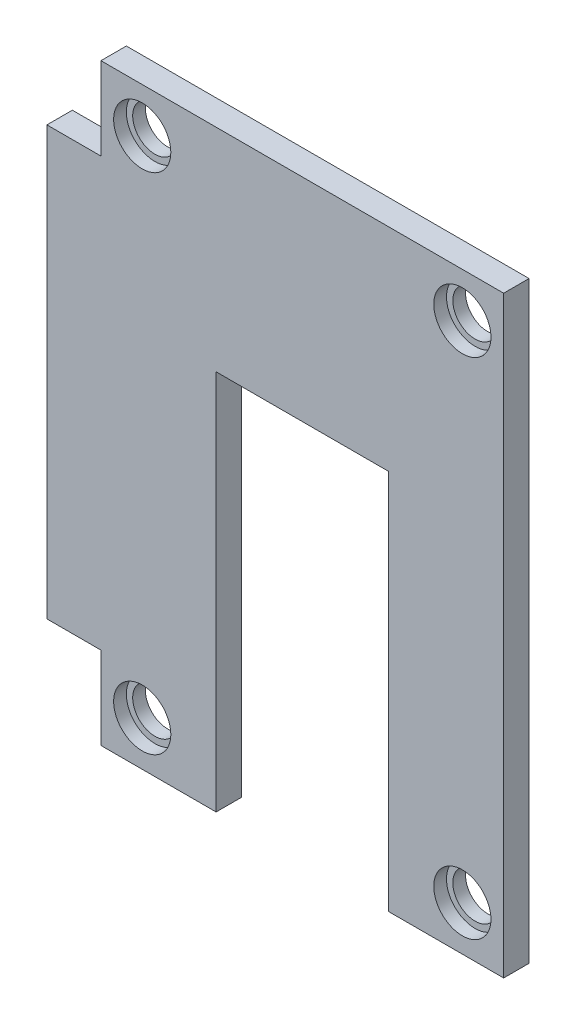
SolidWorks part; units mm, degrees
ref_plane "Alzado" through (0, 0, 0) normal (0, 0, 1) x (1, 0, 0)
ref_plane "Planta" through (0, 0, 0) normal (0, 1, 0) x (1, 0, 0)
ref_plane "Vista lateral" through (0, 0, 0) normal (1, 0, 0) x (0, 0, -1)
sketch "Croquis1" plane through (0, 0, 0) normal (0, 0, 1) x (1, 0, 0)
  line L0 (0, 93.345) -> (64.3868, 93.345)
  line L1 (0, 93.345) -> (0, 0)
  line L2 (0, 0) -> (64.3868, 0)
  line L3 (64.3868, 93.345) -> (64.3868, 0)
  dimension "D1" = 64.3868
  dimension "D2" = 93.345
extrude "Saliente-Extruir1" add sketch "Croquis1" along normal blind 4
sketch "Croquis2" plane through (0, 0, 4) normal (0, 0, 1) x (1, 0, 0)
  line L5 (0, 0) -> (64.3868, 0) construction
  line L6 (18.63, 0) -> (45.7568, 0)
  line L7 (18.63, 0) -> (18.63, 60)
  line L8 (18.63, 60) -> (45.7568, 60)
  line L9 (45.7568, 0) -> (45.7568, 60)
  line L10 (64.3868, 0) -> (64.3868, 93.345) construction
  line L11 (0, 93.345) -> (0, 0) construction
  dimension "D1" = 18.63
  dimension "D2" = 18.63
  dimension "D3" = 60
extrude "Cortar-Extruir1" cut sketch "Croquis2" against normal through all
sketch "Croquis5" plane through (0, 0, 4) normal (0, 0, 1) x (1, 0, 0)
  line L0 (64.3868, 0) -> (64.3868, 93.345) construction
  line L1 (64.3868, 93.345) -> (0, 93.345) construction
  line L2 (0, 93.345) -> (0, 0) construction
  line L3 (45.7568, 0) -> (64.3868, 0) construction
  circle A0 centre (57.3868, 86.345) radius 4.5
  circle A1 centre (7, 86.345) radius 4.5
  circle A2 centre (57.3868, 7) radius 4.5
  circle A3 centre (7, 7) radius 4.5
  dimension "D5" = 9
  dimension "D1" = 7
  dimension "D2" = 7
  dimension "D3" = 7
  dimension "D4" = 7
  dimension "D6" = 7
extrude "Cortar-Extruir3" cut sketch "Croquis5" against normal blind 2
sketch "Croquis6" plane through (0, 0, 2) normal (0, 0, 1) x (1, 0, 0)
  circle A0 centre (7, 86.345) radius 3.5
  circle A1 centre (57.3868, 86.345) radius 3.5
  circle A2 centre (57.3868, 7) radius 3.5
  circle A3 centre (7, 7) radius 3.5
  dimension "D1" = 7
extrude "Cortar-Extruir4" cut sketch "Croquis6" against normal through all
sketch "Croquis7" plane through (0, 0, 0) normal (0, 0, -1) x (-1, 0, 0)
  line L0 (0, 13) -> (0, 80.345)
  line L3 (0, 13) -> (8, 13)
  line L4 (8, 80.345) -> (8, 13)
  line L5 (0, 93.345) -> (0, 0) construction
  line L6 (0, 80.345) -> (8, 80.345)
  line L7 (-64.3868, 93.345) -> (0, 93.345) construction
  dimension "D1" = 8
  dimension "D2" = 13
  dimension "D3" = 13
extrude "Saliente-Extruir4" add sketch "Croquis7" against normal through all
sketch "Croquis8" plane through (0, 0, 0) normal (0, 0, -1) x (-1, 0, 0)
  line L0 (-18.63, 60) -> (-18.63, 0) construction
  line L1 (8, 80.345) -> (-18.63, 80.345)
  line L2 (8, 80.345) -> (8, 13)
  line L3 (8, 13) -> (-18.63, 13)
  line L4 (-18.63, 80.345) -> (-18.63, 13)
extrude "Saliente-Extruir5" add sketch "Croquis8" against normal blind 2
sketch "Croquis9" plane through (0, 0, 0) normal (0, 0, -1) x (-1, 0, 0)
  line L0 (-64.3868, 93.345) -> (0, 93.345) construction
  line L1 (-63.8868, 93.345) -> (-0.5, 93.345) construction
  line L2 (-63.8868, 93.345) -> (-63.8868, 0)
  line L3 (-63.8868, 0) -> (-0.5, 0) construction
  line L4 (-0.5, 93.345) -> (-0.5, 0) construction
  line L5 (0, 0) -> (-18.63, 0) construction
  line L6 (0, 93.345) -> (0, 80.345) construction
  line L7 (-64.3868, 0) -> (-64.3868, 93.345) construction
  line L8 (-0.5, 93.345) -> (0, 93.345)
  line L9 (0, 93.345) -> (0, 80.345)
  line L10 (0, 80.345) -> (-0.5, 80.345)
  line L11 (-0.5, 0) -> (0, 0)
  line L12 (0, 0) -> (0, 13)
  line L13 (0, 13) -> (-0.5, 13)
  line L14 (8, 13) -> (0, 13) construction
  line L15 (-63.8868, 93.345) -> (-64.3868, 93.345)
  line L16 (-64.3868, 93.345) -> (-64.3868, 0)
  line L17 (-64.3868, 0) -> (-63.8868, 0)
  line L18 (-0.5, 13) -> (-0.5, 0)
  line L19 (-0.5, 80.345) -> (-0.5, 93.345)
  dimension "D1" = 0.5
  dimension "D2" = 0.5
extrude "Cortar-Extruir5" cut sketch "Croquis9" against normal blind 13
sketch "Croquis10" plane through (0, 0, 0) normal (0, 0, -1) x (-1, 0, 0)
  line L0 (8, 80.345) -> (-0.5, 80.345) construction
  line L1 (2, 56.345) -> (7, 56.345)
  line L2 (2, 56.345) -> (2, 36.345)
  line L3 (2, 36.345) -> (7, 36.345)
  line L4 (7, 56.345) -> (7, 36.345)
  line L5 (8, 13) -> (8, 80.345) construction
  dimension "D1" = 24
  dimension "D2" = 20
  dimension "D3" = 1
  dimension "D4" = 5
extrude "Saliente-Extruir6" add sketch "Croquis10" along normal blind 25
fillet "Redondeo1" radius 1 1 edges at (-7, 46.345, 0)
fillet "Redondeo2" radius 5 2 edges at (-5, 56.345, 0) (-5, 36.345, 0)
sketch "Croquis11" plane through (-7, 0, 0) normal (-1, 0, 0) x (0, 0, 1)
  line L0 (-25, 56.345) -> (-5, 56.345) construction
  line L1 (-22, 56.345) -> (0, 56.345) construction
  line L2 (-22, 56.345) -> (-22, 36.345) construction
  line L3 (-22, 36.345) -> (0, 36.345) construction
  line L4 (0, 56.345) -> (0, 36.345) construction
  line L5 (0, 31.345) -> (0, 61.345) construction
  line L6 (-25, 36.345) -> (-5, 36.345) construction
  circle A0 centre (-19.75, 46.345) radius 1.5
  circle A1 centre (-2.25, 46.345) radius 1.5
  point P14 (0, 0)
  point P15 (0, 0)
  point P16 (-22, 46.345)
  dimension "D4" = 3
  dimension "D5" = 3
  dimension "D1" = 22
  dimension "D2" = 17.5
  dimension "D3" = 2.25
extrude "Cortar-Extruir6" cut sketch "Croquis11" against normal through all both and the other way through all
